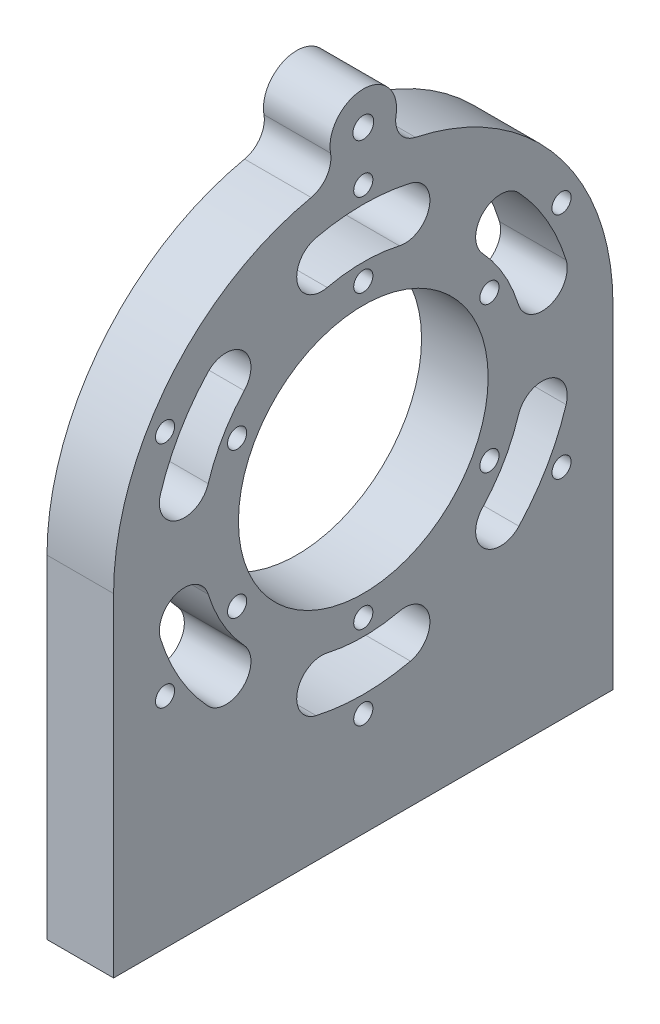
SolidWorks part; units mm, degrees
material "6061 Alloy"
ref_plane "前视基准面" through (0, 0, 0) normal (0, 0, 1) x (1, 0, 0)
ref_plane "上视基准面" through (0, 0, 0) normal (0, 1, 0) x (1, 0, 0)
ref_plane "右视基准面" through (0, 0, 0) normal (1, 0, 0) x (0, 0, -1)
sketch "草图1" plane through (0, 0, 0) normal (1, 0, 0) x (0, 0, -1)
  line L0 (-30, 0) -> (-30, -40)
  line L1 (-30, -40) -> (30, -40)
  line L2 (30, -40) -> (30, 0)
  arc A0 (-6.265, 29.3385) -> (6.265, 29.3385) centre (0, 0) ccw
  circle A1 centre (0, 0) radius 15
  circle A3 centre (0, 33.5) radius 1.25
  arc A4 (3.938, 32.7985) -> (-3.938, 32.7985) centre (0, 33.5) ccw
  arc A5 (3.938, 32.7985) -> (6.265, 29.3385) centre (6.8915, 32.2724) ccw
  arc A6 (-6.265, 29.3385) -> (-3.938, 32.7985) centre (-6.8915, 32.2724) ccw
  circle B0 centre (23.8157, -13.75) radius 1.15
  circle B1 centre (15.1554, -8.75) radius 1.15
  circle B2 centre (0, 0) radius 15
  arc B3 (18.6319, 5.7534) -> (24.3648, 7.5237) centre (21.4984, 6.6386) ccw
  arc B4 (18.6319, 5.7534) -> (14.2986, 13.259) centre (0, 0) ccw
  arc B5 (18.6981, 17.3387) -> (14.2986, 13.259) centre (16.4984, 15.2988) ccw
  arc B6 (24.3648, 7.5237) -> (18.6981, 17.3387) centre (0, 0) ccw
  arc B7 (-4.3333, -19.0124) -> (-5.6667, -24.8624) centre (-5, -21.9374) ccw
  arc B8 (-4.3333, -19.0124) -> (4.3333, -19.0124) centre (0, 0) ccw
  arc B9 (5.6667, -24.8624) -> (4.3333, -19.0124) centre (5, -21.9374) ccw
  arc B10 (-5.6667, -24.8624) -> (5.6667, -24.8624) centre (0, 0) ccw
  arc B11 (-18.6319, -5.7534) -> (-24.3648, -7.5237) centre (-21.4984, -6.6386) ccw
  arc B12 (-18.6319, -5.7534) -> (-14.2986, -13.259) centre (0, 0) ccw
  arc B13 (-18.6981, -17.3387) -> (-14.2986, -13.259) centre (-16.4984, -15.2988) ccw
  arc B14 (-24.3648, -7.5237) -> (-18.6981, -17.3387) centre (0, 0) ccw
  arc B15 (4.3333, 19.0124) -> (5.6667, 24.8624) centre (5, 21.9374) ccw
  arc B16 (4.3333, 19.0124) -> (-4.3333, 19.0124) centre (0, 0) ccw
  arc B17 (-5.6667, 24.8624) -> (-4.3333, 19.0124) centre (-5, 21.9374) ccw
  arc B18 (5.6667, 24.8624) -> (-5.6667, 24.8624) centre (0, 0) ccw
  circle B19 centre (15.1554, 8.75) radius 1.15
  arc B20 (-14.2986, 13.259) -> (-18.6981, 17.3387) centre (-16.4984, 15.2988) ccw
  arc B21 (-14.2986, 13.259) -> (-18.6319, 5.7534) centre (0, 0) ccw
  arc B22 (-24.3648, 7.5237) -> (-18.6319, 5.7534) centre (-21.4984, 6.6386) ccw
  arc B23 (-18.6981, 17.3387) -> (-24.3648, 7.5237) centre (0, 0) ccw
  circle B24 centre (0, -17.5) radius 1.15
  circle B25 centre (-23.8157, -13.75) radius 1.15
  circle B26 centre (-15.1554, -8.75) radius 1.15
  circle B27 centre (-23.8157, 13.75) radius 1.15
  circle B28 centre (23.8157, 13.75) radius 1.15
  circle B29 centre (0, 17.5) radius 1.15
  circle B30 centre (0, 27.5) radius 1.15
  circle B31 centre (-15.1554, 8.75) radius 1.15
  circle B32 centre (0, -27.5) radius 1.15
  arc B33 (24.3648, -7.5237) -> (18.6319, -5.7534) centre (21.4984, -6.6386) ccw
  arc B34 (18.6981, -17.3387) -> (24.3648, -7.5237) centre (0, 0) ccw
  arc B35 (14.2986, -13.259) -> (18.6981, -17.3387) centre (16.4984, -15.2988) ccw
  arc B36 (14.2986, -13.259) -> (18.6319, -5.7534) centre (0, 0) ccw
  dimension "D1" = 60
  dimension "D2" = 2.5
  dimension "D3" = 6
  dimension "D4" = 8
  dimension "D5" = 3
  dimension "D6" = 40
sketch_block_instance "块-外骨骼脊髓盘草图-1"
sketch_block "块-外骨骼脊髓盘草图"
extrude "凸台-拉伸1" add sketch "草图1" along normal mid plane 8 contours A6 A0 A5 A4 B32 B31 B30 B29 B28 B27 B26 B25 B24 B23 B20 B21 B22 B19 B18 B15 B16 B17 B14 B11 B12 B13 B10 B7 B8 B9 B6 B3 B4 B5 B1 | A0 L0 L1 L2 region at (0, -30.4172, 0) region at (0, 18.3006, 22.6212)
sketch "草图2" plane through (0, -40, 0) normal (0, -1, 0) x (1, 0, 0)
  line L1 (4, 30) -> (4, -30) construction
  circle A0 centre (0, 22.5) radius 1.5
  circle A1 centre (0, -22.5) radius 1.5
  circle A2 centre (0, 0) radius 1.5
  dimension "D1" = 3
  dimension "D2" = 3
  dimension "D3" = 45
  dimension "D7" = 3
  dimension "D4" = 22.5
  dimension "D5" = 4
  dimension "D6" = 4
hole_wizard "M3 螺纹孔1" positions "3D草图1" profile "草图3" tap size "M3" standard "GB"
sketch3d "3D草图1"
  point P0 (0, -40, 22.5)
  point P3 (0, -40, 0)
  point P6 (0, -40, -22.5)
sketch "草图3" plane through (0, -40, 22.5) normal (1, 0, 0) x (0, 0, -1)
  line L0 (0, 0) -> (0, 8.2511)
  line L1 (0, 8.2511) -> (1.25, 7.5)
  line L2 (1.25, 7.5) -> (1.25, 0)
  line L5 (1.25, 0) -> (0, 0)
  line L10 (0, 8.2511) -> (-1.25, 7.5) construction
  line L11 (0, -6.35) -> (0, 107.95) construction
  dimension "螺纹孔钻头直径" = 2.5
  dimension "螺纹孔钻头深度" = 7.5
  dimension "导头角度" = 118
cosmetic thread "孔螺蚊线1" parameters "D1"=6, "D2"=3
cosmetic thread "孔螺蚊线2" parameters "D1"=6, "D2"=3
cosmetic thread "孔螺蚊线3" parameters "D1"=6, "D2"=3
